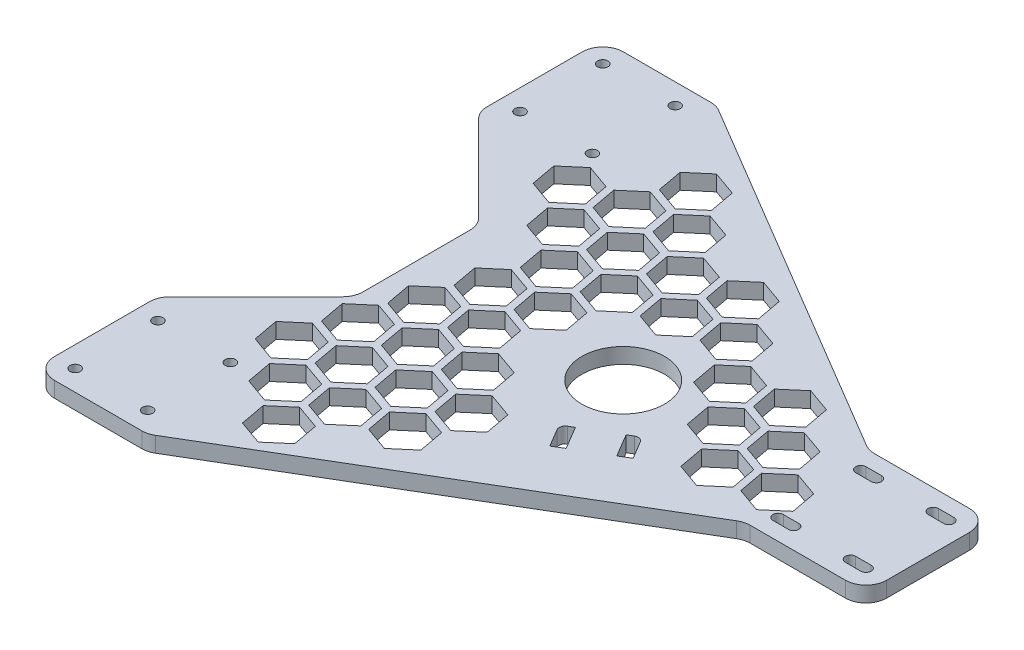
SolidWorks part; units mm, degrees
material "6061-O (SS)"
ref_plane "Plan de face" through (0, 0, 0) normal (0, 0, 1) x (1, 0, 0)
ref_plane "Plan de dessus" through (0, 0, 0) normal (0, 1, 0) x (1, 0, 0)
ref_plane "Plan de droite" through (0, 0, 0) normal (1, 0, 0) x (0, 0, -1)
sketch "Esquisse1" plane through (0, 0, 0) normal (0, 1, 0) x (1, 0, 0)
  line L1 (58.95, -55) -> (-58.95, -55)
  line L2 (58.95, -55) -> (58.95, 55)
  line L3 (58.95, 55) -> (-58.95, 55)
  line L4 (-58.95, -55) -> (-58.95, 55)
  line L5 (58.95, -55) -> (-58.95, 55) construction
  line L6 (58.95, 55) -> (-58.95, -55) construction
  point P0 (0, 0)
  dimension "D1" = 110
  dimension "D2" = 117.9
extrude "Boss.-Extru.1" add sketch "Esquisse1" along normal blind 3
sketch "Esquisse2" plane through (0, 0, 0) normal (0, 1, 0) x (1, 0, 0)
  line L0 (-58.95, -55) -> (58.95, -55) construction
  line L1 (-54.95, -35) -> (-40.95, -35) construction
  line L2 (-54.95, -35) -> (-54.95, -51) construction
  line L3 (-54.95, -51) -> (-40.95, -51) construction
  line L4 (-40.95, -35) -> (-40.95, -51) construction
  line L5 (-54.95, -35) -> (-40.95, -51) construction
  line L6 (-54.95, -51) -> (-40.95, -35) construction
  line L7 (-58.95, 55) -> (-58.95, -55) construction
  line L8 (0, 0) -> (-58.95, 0) construction
  line L9 (-54.95, 51) -> (-40.95, 35) construction
  line L10 (-54.95, 35) -> (-40.95, 51) construction
  line L11 (-40.95, 35) -> (-40.95, 51) construction
  line L12 (-54.95, 51) -> (-40.95, 51) construction
  line L13 (-54.95, 35) -> (-54.95, 51) construction
  line L14 (-54.95, 35) -> (-40.95, 35) construction
  line L15 (46.45, 0) -> (53.45, 8) construction
  line L16 (39.45, 8) -> (53.45, 8) construction
  line L17 (39.45, 8) -> (39.45, -8) construction
  line L18 (39.45, -8) -> (53.45, -8) construction
  line L19 (53.45, 8) -> (53.45, -8) construction
  line L20 (39.45, 8) -> (46.45, 0) construction
  line L21 (39.45, -8) -> (46.45, 0) construction
  line L22 (46.45, 0) -> (53.45, -8) construction
  line L23 (0, 0) -> (58.95, 0) construction
  line L24 (58.95, -55) -> (58.95, 55) construction
  line L25 (58.95, 12) -> (35.45, 12)
  line L26 (35.45, 12) -> (-36.95, 55)
  line L27 (58.95, 55) -> (-58.95, 55) construction
  line L28 (-36.95, 55) -> (58.95, 55)
  line L29 (58.95, 55) -> (58.95, 12)
  line L30 (58.95, -12) -> (35.45, -12)
  line L31 (58.95, -55) -> (58.95, -12)
  line L32 (-36.95, -55) -> (58.95, -55)
  line L33 (35.45, -12) -> (-36.95, -55)
  line L34 (-58.95, -31) -> (-39.95, -12)
  line L35 (-39.95, -12) -> (-39.95, 12)
  line L36 (-39.95, 12) -> (-58.95, 31)
  line L37 (-58.95, 31) -> (-58.95, -31)
  line L38 (37.95, 8) -> (40.95, 8) construction
  line L39 (37.95, 9) -> (40.95, 9)
  line L40 (37.95, 7) -> (40.95, 7)
  line L41 (54.95, 8) -> (51.95, 8) construction
  line L42 (54.95, 7) -> (51.95, 7)
  line L43 (54.95, 9) -> (51.95, 9)
  line L44 (37.95, -8) -> (40.95, -8) construction
  line L45 (37.95, -7) -> (40.95, -7)
  line L46 (37.95, -9) -> (40.95, -9)
  line L47 (54.95, -8) -> (51.95, -8) construction
  line L48 (54.95, -9) -> (51.95, -9)
  line L49 (54.95, -7) -> (51.95, -7)
  circle A0 centre (-40.95, -35) radius 1
  circle A1 centre (-54.95, -35) radius 1
  circle A2 centre (-54.95, -51) radius 1
  circle A3 centre (-40.95, -51) radius 1
  circle A4 centre (-40.95, 51) radius 1
  circle A5 centre (-54.95, 51) radius 1
  circle A6 centre (-54.95, 35) radius 1
  circle A7 centre (-40.95, 35) radius 1
  arc A12 (37.95, 9) -> (37.95, 7) centre (37.95, 8) ccw
  arc A13 (40.95, 7) -> (40.95, 9) centre (40.95, 8) ccw
  arc A14 (54.95, 7) -> (54.95, 9) centre (54.95, 8) ccw
  arc A15 (51.95, 9) -> (51.95, 7) centre (51.95, 8) ccw
  arc A16 (37.95, -7) -> (37.95, -9) centre (37.95, -8) ccw
  arc A17 (40.95, -9) -> (40.95, -7) centre (40.95, -8) ccw
  arc A18 (54.95, -9) -> (54.95, -7) centre (54.95, -8) ccw
  arc A19 (51.95, -7) -> (51.95, -9) centre (51.95, -8) ccw
  point P0 (-47.95, -43)
  point P25 (-47.95, 43)
  point P26 (46.45, 0)
  point P33 (39.45, 8)
  point P52 (-39.95, 0)
  point P58 (53.45, 8)
  point P65 (39.45, -8)
  point P72 (53.45, -8)
  dimension "D3" = 2
  dimension "D4" = 4
  dimension "D5" = 4
  dimension "D6" = 1
  dimension "D1" = 16
  dimension "D2" = 14
  dimension "D7" = 14
  dimension "D8" = 16
  dimension "D9" = 5.5
  dimension "D10" = 4
  dimension "D11" = 4
  dimension "D12" = 4
  dimension "D13" = 4
  dimension "D14" = 4
  dimension "D15" = 4
  dimension "D16" = 1
  dimension "D17" = 1.5
extrude "Enlèv. mat.-Extru.1" cut sketch "Esquisse2" along normal through all
fillet "Congé1" radius 4 12 edges at (35.45, 1.5, 12) (58.95, 1.5, 12) (58.95, 1.5, -12) (35.45, 1.5, -12) (-36.95, 1.5, -55) (-58.95, 1.5, -55) (-58.95, 1.5, -31) (-39.95, 1.5, -12) (-39.95, 1.5, 12) (-58.95, 1.5, 31) (-58.95, 1.5, 55) (-36.95, 1.5, 55)
sketch "Esquisse3" plane through (0, 0, 0) normal (0, 1, 0) x (1, 0, 0)
  line L1 (11, -11) -> (-11, -11) construction
  line L2 (11, -11) -> (11, 11) construction
  line L3 (11, 11) -> (-11, 11) construction
  line L4 (-11, -11) -> (-11, 11) construction
  line L5 (11, -11) -> (-11, 11) construction
  line L6 (11, 11) -> (-11, -11) construction
  line L7 (-11.5, 11) -> (-10.5, 11) construction
  line L8 (-11.5, 13) -> (-10.5, 13)
  line L9 (-11.5, 9) -> (-10.5, 9)
  line L10 (0, 0) -> (-11, 0) construction
  line L11 (0, 0) -> (0, 11) construction
  line L12 (11.5, 11) -> (10.5, 11) construction
  line L13 (11.5, 13) -> (10.5, 13)
  line L14 (11.5, 9) -> (10.5, 9)
  line L15 (11.5, -11) -> (10.5, -11) construction
  line L16 (11.5, -13) -> (10.5, -13)
  line L17 (11.5, -9) -> (10.5, -9)
  line L18 (-11.5, -11) -> (-10.5, -11) construction
  line L19 (-11.5, -13) -> (-10.5, -13)
  line L20 (-11.5, -9) -> (-10.5, -9)
  arc A4 (-11.5, 13) -> (-11.5, 9) centre (-11.5, 11) ccw
  arc A5 (-10.5, 9) -> (-10.5, 13) centre (-10.5, 11) ccw
  arc A6 (11.5, 13) -> (11.5, 9) centre (11.5, 11) cw
  arc A7 (10.5, 9) -> (10.5, 13) centre (10.5, 11) cw
  arc A8 (11.5, -13) -> (11.5, -9) centre (11.5, -11) ccw
  arc A9 (10.5, -9) -> (10.5, -13) centre (10.5, -11) ccw
  arc A10 (-11.5, -13) -> (-11.5, -9) centre (-11.5, -11) cw
  arc A11 (-10.5, -9) -> (-10.5, -13) centre (-10.5, -11) cw
  circle A12 centre (0, 0) radius 8
  point P0 (0, 0)
  point P8 (-11, 11)
  point P22 (11, 11)
  point P29 (11, -11)
  point P36 (-11, -11)
  dimension "D3" = 2
  dimension "D6" = 16
  dimension "D1" = 22
  dimension "D2" = 22
  dimension "D5" = 0.5
extrude "Enlèv. mat.-Extru.2" cut sketch "Esquisse3" along normal through all contours A12
sketch "Esquisse4" plane through (0, 0, 0) normal (0, -1, 0) x (1, 0, 0)
  line L4 (0, 0) -> (6.2905, 0) construction
  line L11 (3.9234, 18.1109) -> (1.8808, 14.6717)
  line L13 (2.2823, 13.0957) -> (3.2711, 12.5085)
  line L18 (3.2711, 12.5085) -> (5.9009, 16.9364)
  line L19 (5.9009, 16.9364) -> (3.9234, 18.1109)
  line L21 (4.586, 14.7224) -> (10.7335, 11.0713) construction
  line L22 (7.939, 13.3671) -> (7.3805, 12.4266) construction
  line L23 (1.2935, 13.6829) -> (3.2711, 12.5085) construction
  line L24 (34.5057, 12.5608) -> (-36.0057, 54.4392) construction
  line L25 (1.2935, 13.6829) -> (1.8808, 14.6717) construction
  line L26 (9.4186, 8.8573) -> (12.0484, 13.2852)
  line L27 (10.4073, 8.2701) -> (9.4186, 8.8573)
  line L28 (14.0259, 12.1107) -> (11.9833, 8.6716)
  line L29 (12.0484, 13.2852) -> (14.0259, 12.1107)
  line L36 (-36.0057, -54.4392) -> (34.5057, -12.5608) construction
  line L37 (-20.806, -41.8884) -> (-19.896, -36.9719)
  line L38 (-19.896, -36.9719) -> (-23.6988, -33.7255)
  line L39 (-23.6988, -33.7255) -> (-28.4116, -35.3956)
  line L40 (-28.4116, -35.3956) -> (-29.3216, -40.3121)
  line L41 (-29.3216, -40.3121) -> (-25.5189, -43.5585)
  line L42 (-25.5189, -43.5585) -> (-20.806, -41.8884)
  line L91 (-39.95, 0) -> (-65.3468, 0) construction
  line L92 (-24.2263, -32.4915) -> (-23.3162, -27.575)
  line L153 (-23.3162, -27.575) -> (-27.119, -24.3286)
  line L154 (-27.119, -24.3286) -> (-31.8318, -25.9987)
  line L155 (-31.8318, -25.9987) -> (-32.7418, -30.9152)
  line L156 (-32.7418, -30.9152) -> (-28.9391, -34.1616)
  line L157 (-28.9391, -34.1616) -> (-24.2263, -32.4915)
  line L158 (-27.6465, -23.0945) -> (-26.7364, -18.178)
  line L159 (-26.7364, -18.178) -> (-30.5392, -14.9317)
  line L160 (-30.5392, -14.9317) -> (-35.252, -16.6018)
  line L161 (-35.252, -16.6018) -> (-36.162, -21.5183)
  line L162 (-36.162, -21.5183) -> (-32.3593, -24.7646)
  line L163 (-32.3593, -24.7646) -> (-27.6465, -23.0945)
  line L164 (-14.3782, -34.2279) -> (-13.4681, -29.3115)
  line L165 (-13.4681, -29.3115) -> (-17.2709, -26.0651)
  line L166 (-17.2709, -26.0651) -> (-21.9837, -27.7352)
  line L167 (-21.9837, -27.7352) -> (-22.8938, -32.6517)
  line L168 (-22.8938, -32.6517) -> (-19.091, -35.898)
  line L169 (-19.091, -35.898) -> (-14.3782, -34.2279)
  line L170 (-17.8041, -24.8152) -> (-16.8941, -19.8987)
  line L171 (-16.8941, -19.8987) -> (-20.6968, -16.6524)
  line L172 (-20.6968, -16.6524) -> (-25.4097, -18.3225)
  line L173 (-25.4097, -18.3225) -> (-26.3197, -23.239)
  line L174 (-26.3197, -23.239) -> (-22.5169, -26.4853)
  line L175 (-22.5169, -26.4853) -> (-17.8041, -24.8152)
  line L176 (-34.0743, -30.755) -> (-33.1643, -25.8385)
  line L177 (-33.1643, -25.8385) -> (-36.967, -22.5921)
  line L178 (-36.967, -22.5921) -> (-41.6799, -24.2622)
  line L179 (-41.6799, -24.2622) -> (-42.5899, -29.1787)
  line L180 (-42.5899, -29.1787) -> (-38.7872, -32.4251)
  line L181 (-38.7872, -32.4251) -> (-34.0743, -30.755)
  line L182 (-11.3762, -17.1548) -> (-10.4662, -12.2383)
  line L183 (-10.4662, -12.2383) -> (-14.269, -8.9919)
  line L184 (-14.269, -8.9919) -> (-18.9818, -10.662)
  line L185 (-18.9818, -10.662) -> (-19.8918, -15.5785)
  line L186 (-19.8918, -15.5785) -> (-16.0891, -18.8249)
  line L187 (-16.0891, -18.8249) -> (-11.3762, -17.1548)
  line L188 (-21.2243, -15.4183) -> (-20.3143, -10.5018)
  line L189 (-20.3143, -10.5018) -> (-24.117, -7.2554)
  line L190 (-24.117, -7.2554) -> (-28.8299, -8.9256)
  line L191 (-28.8299, -8.9256) -> (-29.7399, -13.842)
  line L192 (-29.7399, -13.842) -> (-25.9371, -17.0884)
  line L193 (-25.9371, -17.0884) -> (-21.2243, -15.4183)
  line L194 (-24.6388, -6.0372) -> (-23.7287, -1.1207)
  line L195 (-23.7287, -1.1207) -> (-27.5315, 2.1257)
  line L196 (-27.5315, 2.1257) -> (-32.2443, 0.4556)
  line L197 (-32.2443, 0.4556) -> (-33.1544, -4.4609)
  line L198 (-33.1544, -4.4609) -> (-29.3516, -7.7073)
  line L199 (-29.3516, -7.7073) -> (-24.6388, -6.0372)
  line L200 (-14.7907, -7.7736) -> (-13.8806, -2.8572)
  line L201 (-13.8806, -2.8572) -> (-17.6834, 0.3892)
  line L202 (-17.6834, 0.3892) -> (-22.3962, -1.2809)
  line L203 (-22.3962, -1.2809) -> (-23.3063, -6.1974)
  line L204 (-23.3063, -6.1974) -> (-19.5035, -9.4438)
  line L205 (-19.5035, -9.4438) -> (-14.7907, -7.7736)
  line L206 (-18.2109, 1.6233) -> (-17.3008, 6.5398)
  line L207 (-17.3008, 6.5398) -> (-21.1036, 9.7861)
  line L208 (-21.1036, 9.7861) -> (-25.8164, 8.116)
  line L209 (-25.8164, 8.116) -> (-26.7265, 3.1995)
  line L210 (-26.7265, 3.1995) -> (-22.9237, -0.0468)
  line L211 (-22.9237, -0.0468) -> (-18.2109, 1.6233)
  line L212 (-21.6311, 11.0202) -> (-20.7211, 15.9367)
  line L213 (-20.7211, 15.9367) -> (-24.5238, 19.1831)
  line L214 (-24.5238, 19.1831) -> (-29.2366, 17.513)
  line L215 (-29.2366, 17.513) -> (-30.1467, 12.5965)
  line L216 (-30.1467, 12.5965) -> (-26.3439, 9.3501)
  line L217 (-26.3439, 9.3501) -> (-21.6311, 11.0202)
  line L218 (-25.0513, 20.4171) -> (-24.1413, 25.3336)
  line L219 (-24.1413, 25.3336) -> (-27.944, 28.58)
  line L220 (-27.944, 28.58) -> (-32.6568, 26.9099)
  line L221 (-32.6568, 26.9099) -> (-33.5669, 21.9934)
  line L222 (-33.5669, 21.9934) -> (-29.7641, 18.747)
  line L223 (-29.7641, 18.747) -> (-25.0513, 20.4171)
  line L224 (-28.4715, 29.8141) -> (-27.5615, 34.7305)
  line L225 (-27.5615, 34.7305) -> (-31.3642, 37.9769)
  line L226 (-31.3642, 37.9769) -> (-36.0771, 36.3068)
  line L227 (-36.0771, 36.3068) -> (-36.9871, 31.3903)
  line L228 (-36.9871, 31.3903) -> (-33.1843, 28.144)
  line L229 (-33.1843, 28.144) -> (-28.4715, 29.8141)
  line L230 (-28.059, 3.3598) -> (-27.1489, 8.2763)
  line L231 (-27.1489, 8.2763) -> (-30.9517, 11.5226)
  line L232 (-30.9517, 11.5226) -> (-35.6645, 9.8525)
  line L233 (-35.6645, 9.8525) -> (-36.5746, 4.936)
  line L234 (-36.5746, 4.936) -> (-32.7718, 1.6897)
  line L235 (-32.7718, 1.6897) -> (-28.059, 3.3598)
  line L236 (-15.2032, 18.6807) -> (-14.2932, 23.5971)
  line L237 (-14.2932, 23.5971) -> (-18.0959, 26.8435)
  line L238 (-18.0959, 26.8435) -> (-22.8088, 25.1734)
  line L239 (-22.8088, 25.1734) -> (-23.7188, 20.2569)
  line L240 (-23.7188, 20.2569) -> (-19.9161, 17.0105)
  line L241 (-19.9161, 17.0105) -> (-15.2032, 18.6807)
  line L242 (-8.7754, 26.3411) -> (-7.8653, 31.2576)
  line L243 (-7.8653, 31.2576) -> (-11.6681, 34.504)
  line L244 (-11.6681, 34.504) -> (-16.3809, 32.8338)
  line L245 (-16.3809, 32.8338) -> (-17.2909, 27.9174)
  line L246 (-17.2909, 27.9174) -> (-13.4882, 24.671)
  line L247 (-13.4882, 24.671) -> (-8.7754, 26.3411)
  line L248 (-18.6234, 28.0776) -> (-17.7134, 32.9941)
  line L249 (-17.7134, 32.9941) -> (-21.5161, 36.2404)
  line L250 (-21.5161, 36.2404) -> (-26.229, 34.5703)
  line L251 (-26.229, 34.5703) -> (-27.139, 29.6538)
  line L252 (-27.139, 29.6538) -> (-23.3363, 26.4075)
  line L253 (-23.3363, 26.4075) -> (-18.6234, 28.0776)
  line L254 (-22.0436, 37.4745) -> (-21.1336, 42.391)
  line L255 (-21.1336, 42.391) -> (-24.9363, 45.6374)
  line L256 (-24.9363, 45.6374) -> (-29.6492, 43.9672)
  line L257 (-29.6492, 43.9672) -> (-30.5592, 39.0508)
  line L258 (-30.5592, 39.0508) -> (-26.7565, 35.8044)
  line L259 (-26.7565, 35.8044) -> (-22.0436, 37.4745)
  line L260 (-34.8994, 22.1536) -> (-33.9893, 27.0701)
  line L261 (-33.9893, 27.0701) -> (-37.7921, 30.3165)
  line L262 (-37.7921, 30.3165) -> (-42.5049, 28.6464)
  line L263 (-42.5049, 28.6464) -> (-43.415, 23.7299)
  line L264 (-43.415, 23.7299) -> (-39.6122, 20.4835)
  line L265 (-39.6122, 20.4835) -> (-34.8994, 22.1536)
  line L266 (-31.4792, 12.7567) -> (-30.5691, 17.6732)
  line L267 (-30.5691, 17.6732) -> (-34.3719, 20.9195)
  line L268 (-34.3719, 20.9195) -> (-39.0847, 19.2494)
  line L269 (-39.0847, 19.2494) -> (-39.9948, 14.333)
  line L270 (-39.9948, 14.333) -> (-36.192, 11.0866)
  line L271 (-36.192, 11.0866) -> (-31.4792, 12.7567)
  line L272 (-11.783, 9.2837) -> (-10.873, 14.2002)
  line L273 (-10.873, 14.2002) -> (-14.6757, 17.4466)
  line L274 (-14.6757, 17.4466) -> (-19.3886, 15.7765)
  line L275 (-19.3886, 15.7765) -> (-20.2986, 10.86)
  line L276 (-20.2986, 10.86) -> (-16.4959, 7.6136)
  line L277 (-16.4959, 7.6136) -> (-11.783, 9.2837)
  line L278 (-7.956, -26.5517) -> (-7.046, -21.6352)
  line L279 (-7.046, -21.6352) -> (-10.8488, -18.3889)
  line L280 (-10.8488, -18.3889) -> (-15.5616, -20.059)
  line L281 (-15.5616, -20.059) -> (-16.4716, -24.9755)
  line L282 (-16.4716, -24.9755) -> (-12.6689, -28.2218)
  line L283 (-12.6689, -28.2218) -> (-7.956, -26.5517)
  line L284 (-1.5282, -18.8913) -> (-0.6181, -13.9748)
  line L285 (-0.6181, -13.9748) -> (-4.4209, -10.7284)
  line L286 (-4.4209, -10.7284) -> (-9.1337, -12.3985)
  line L287 (-9.1337, -12.3985) -> (-10.0438, -17.315)
  line L288 (-10.0438, -17.315) -> (-6.241, -20.5614)
  line L289 (-6.241, -20.5614) -> (-1.5282, -18.8913)
  line L290 (8.3199, -20.6277) -> (9.23, -15.7113)
  line L291 (9.23, -15.7113) -> (5.4272, -12.4649)
  line L292 (5.4272, -12.4649) -> (0.7144, -14.135)
  line L293 (0.7144, -14.135) -> (-0.1957, -19.0515)
  line L294 (-0.1957, -19.0515) -> (3.6071, -22.2979)
  line L295 (3.6071, -22.2979) -> (8.3199, -20.6277)
  line L296 (14.7478, -12.9673) -> (15.6578, -8.0508)
  line L297 (15.6578, -8.0508) -> (11.8551, -4.8044)
  line L298 (11.8551, -4.8044) -> (7.1422, -6.4746)
  line L299 (7.1422, -6.4746) -> (6.2322, -11.391)
  line L300 (6.2322, -11.391) -> (10.035, -14.6374)
  line L301 (10.035, -14.6374) -> (14.7478, -12.9673)
  line L302 (21.1757, -5.3069) -> (22.0857, -0.3904)
  line L303 (22.0857, -0.3904) -> (18.2829, 2.856)
  line L304 (18.2829, 2.856) -> (13.5701, 1.1859)
  line L305 (13.5701, 1.1859) -> (12.6601, -3.7306)
  line L306 (12.6601, -3.7306) -> (16.4628, -6.977)
  line L307 (16.4628, -6.977) -> (21.1757, -5.3069)
  line L308 (27.6035, 2.3536) -> (28.5136, 7.2701)
  line L309 (28.5136, 7.2701) -> (24.7108, 10.5164)
  line L310 (24.7108, 10.5164) -> (19.998, 8.8463)
  line L311 (19.998, 8.8463) -> (19.0879, 3.9298)
  line L312 (19.0879, 3.9298) -> (22.8907, 0.6835)
  line L313 (22.8907, 0.6835) -> (27.6035, 2.3536)
  line L314 (24.5959, -14.7038) -> (25.5059, -9.7873)
  line L315 (25.5059, -9.7873) -> (21.7031, -6.5409)
  line L316 (21.7031, -6.5409) -> (16.9903, -8.211)
  line L317 (16.9903, -8.211) -> (16.0803, -13.1275)
  line L318 (16.0803, -13.1275) -> (19.883, -16.3739)
  line L319 (19.883, -16.3739) -> (24.5959, -14.7038)
  line L320 (31.0237, -7.0433) -> (31.9338, -2.1269)
  line L321 (31.9338, -2.1269) -> (28.131, 1.1195)
  line L322 (28.131, 1.1195) -> (23.4182, -0.5506)
  line L323 (23.4182, -0.5506) -> (22.5081, -5.4671)
  line L324 (22.5081, -5.4671) -> (26.3109, -8.7135)
  line L325 (26.3109, -8.7135) -> (31.0237, -7.0433)
  line L326 (37.4516, 0.6171) -> (38.3617, 5.5336)
  line L327 (38.3617, 5.5336) -> (34.5589, 8.78)
  line L328 (34.5589, 8.78) -> (29.8461, 7.1098)
  line L329 (29.8461, 7.1098) -> (28.936, 2.1934)
  line L330 (28.936, 2.1934) -> (32.7388, -1.053)
  line L331 (32.7388, -1.053) -> (37.4516, 0.6171)
  line L332 (-5.3551, 16.9442) -> (-4.4451, 21.8607)
  line L333 (-4.4451, 21.8607) -> (-8.2479, 25.107)
  line L334 (-8.2479, 25.107) -> (-12.9607, 23.4369)
  line L335 (-12.9607, 23.4369) -> (-13.8707, 18.5204)
  line L336 (-13.8707, 18.5204) -> (-10.068, 15.2741)
  line L337 (-10.068, 15.2741) -> (-5.3551, 16.9442)
  line L338 (1.892, -28.2882) -> (2.8021, -23.3717)
  line L339 (2.8021, -23.3717) -> (-1.0007, -20.1253)
  line L340 (-1.0007, -20.1253) -> (-5.7135, -21.7954)
  line L341 (-5.7135, -21.7954) -> (-6.6236, -26.7119)
  line L342 (-6.6236, -26.7119) -> (-2.8208, -29.9583)
  line L343 (-2.8208, -29.9583) -> (1.892, -28.2882)
  arc A14 (2.2823, 13.0957) -> (1.8808, 14.6717) centre (2.8695, 14.0845) cw
  arc A15 (10.4073, 8.2701) -> (11.9833, 8.6716) centre (10.9946, 9.2588) ccw
  circle A16 centre (-24.6088, -38.642) radius 4.3301 construction
  point P8 (7.6597, 12.8968)
  point P37 (1.2935, 13.6829)
  dimension "D1" = 7.15
  dimension "D2" = 5.15
  dimension "D3" = 2.3
  dimension "D5" = 1.15
  dimension "D12" = 2
  dimension "D13" = 2
  dimension "D4" = 15
  dimension "D6" = 5
  dimension "D7" = 3
  dimension "D8" = 2
  dimension "D9" = 2
  dimension "D10" = 2
  dimension "D11" = 2
  dimension "D21" = 4
  dimension "D25" = 11.194
  dimension "D14" = 2
  dimension "D16" = 2
  dimension "D15" = 2
  dimension "D18" = 5
  dimension "D17" = 2
  dimension "D19" = 3
  dimension "D20" = 2
  dimension "D22" = 2
  dimension "D23" = 3
  dimension "D24" = 2
extrude "Enlèv. mat.-Extru.3" cut sketch "Esquisse4" against normal through all
